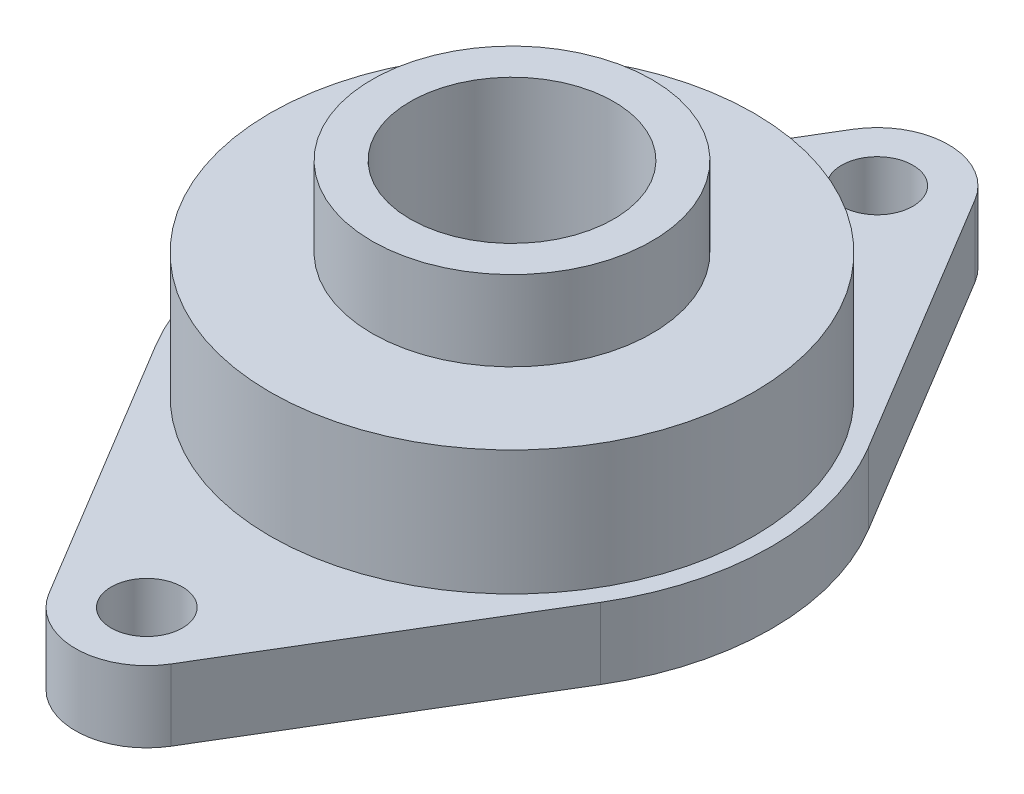
SolidWorks part; units mm, degrees
ref_plane "Front Plane" through (0, 0, 0) normal (0, 0, 1) x (1, 0, 0)
ref_plane "Top Plane" through (0, 0, 0) normal (0, 1, 0) x (1, 0, 0)
ref_plane "Right Plane" through (0, 0, 0) normal (1, 0, 0) x (0, 0, -1)
sketch "Sketch1" plane through (0, 0, 0) normal (0, 1, 0) x (1, 0, 0)
  line L0 (0, 85.75) -> (0, -85.75) construction
  line L1 (-51, 85.75) -> (51, 85.75)
  line L2 (-51, 85.75) -> (-51, -85.75)
  line L3 (-51, -85.75) -> (51, -85.75)
  line L4 (51, 85.75) -> (51, -85.75)
  line L5 (-51, 85.75) -> (51, -85.75) construction
  line L6 (-51, -85.75) -> (51, 85.75) construction
  line L7 (-51, 0) -> (51, 0) construction
  line L8 (-43.6959, 26.2997) -> (-11.9949, 78.9695)
  line L9 (11.9949, 78.9695) -> (43.6959, 26.2997)
  line L10 (-43.6959, -26.2997) -> (-11.9949, -78.9695)
  line L11 (11.9949, -78.9695) -> (43.6959, -26.2997)
  circle A0 centre (0, 71.75) radius 7
  circle A1 centre (0, -71.75) radius 7
  circle A2 centre (0, 0) radius 20
  circle A3 centre (0, 71.75) radius 14
  circle A4 centre (0, -71.75) radius 14
  circle A5 centre (0, 0) radius 51
  point P0 (0, 0)
  dimension "D2" = 14
  dimension "D5" = 40
  dimension "D1" = 171.5
  dimension "D3" = 143.5
  dimension "D4" = 102
extrude "Boss-Extrude1" add sketch "Sketch1" along normal blind 14 contours A3 A0 | A5 L9 A3 L8 | A5 L10 A4 L11 | A4 A1 | A5 A2 region at (6.6945, 0, -83.5928) region at (-47.7502, 0, -13.2615) region at (0, 0, -54.4996) region at (0, 0, 54.4996) region at (-6.6945, 0, 83.5928)
sketch "Sketch2" plane through (0, 14, 0) normal (0, 1, 0) x (1, 0, 0)
  circle A0 centre (0, 0) radius 47.5
  circle A2 centre (0, 0) radius 20
  circle A3 centre (0, 0) radius 20 construction
  dimension "D1" = 95
extrude "Boss-Extrude2" add sketch "Sketch2" along normal offset from surface (24.5 mm away) 38.5 up to face at (0, 0, 0)
sketch "Sketch3" plane through (0, 38.5, 0) normal (0, 1, 0) x (1, 0, 0)
  circle A0 centre (0, 0) radius 20 construction
  circle A1 centre (0, 0) radius 20
  circle A2 centre (0, 0) radius 27.5
  dimension "D1" = 55
extrude "Boss-Extrude3" add sketch "Sketch3" along normal offset from surface (15.7 mm away) 54.2 up to face at (0, 0, 0)
